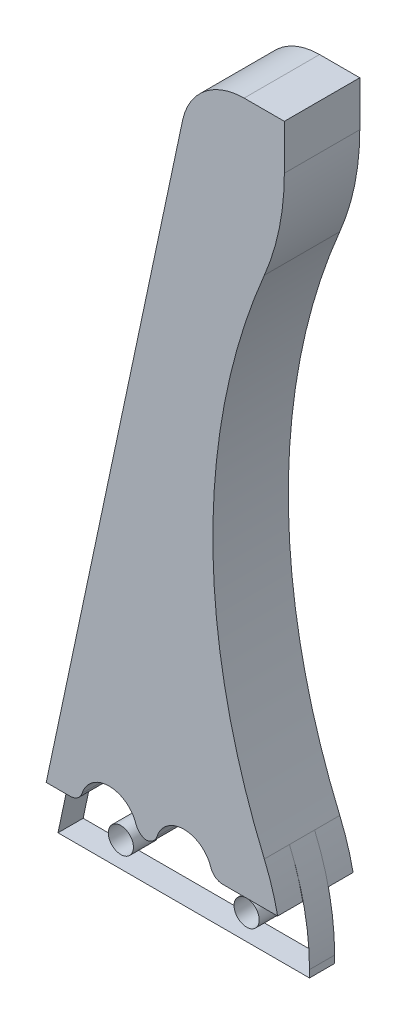
SolidWorks part; units mm, degrees
ref_plane "Alzado" through (0, 0, 0) normal (0, 0, 1) x (1, 0, 0)
ref_plane "Planta" through (0, 0, 0) normal (0, 1, 0) x (1, 0, 0)
ref_plane "Vista lateral" through (0, 0, 0) normal (1, 0, 0) x (0, 0, -1)
sketch "Croquis1" plane through (0, 0, 0) normal (0, 0, 1) x (1, 0, 0)
  line L0 (0, 0) -> (20, 0)
  line L5 (0, 0) -> (12.7534, 60)
  line L6 (12.7534, 60) -> (20, 60)
  line L7 (20, 60) -> (20, 52)
  line L8 (20, 0) -> (20, 5)
  arc A2 (20, 52) -> (20, 5) centre (65.7262, 28.5) ccw
  dimension "D5" = 60
  dimension "D1" = 78
  dimension "D2" = 20
  dimension "D3" = 5
  dimension "D4" = 8
  dimension "D6" = 0
extrude "Saliente-Extruir1" add sketch "Croquis1" along normal blind 2
fillet "Redondeo1" radius 5 1 edges at (12.7534, 60, 1)
fillet "Redondeo2" radius 20 1 edges at (20, 52, 1)
fillet "Redondeo3" radius 20 1 edges at (20, 5, 1)
sketch "Croquis3" plane through (0, 0, 2) normal (0, 0, 1) x (1, 0, 0)
  line L0 (0, 0) -> (20, 0) construction
  circle A0 centre (5, 2) radius 1
  circle A1 centre (15, 2) radius 1
  dimension "D1" = 2
  dimension "D2" = 2
  dimension "D3" = 5
  dimension "D5" = 10
  dimension "D4" = 2
extrude "Cortar-Extruir1" cut sketch "Croquis3" against normal blind 2
sketch "Croquis4" plane through (0, 0, 2) normal (0, 0, 1) x (1, 0, 0)
  line L0 (1.0628, 5) -> (19.4673, 5)
  line L1 (11.9116, 56.0396) -> (0, 0) construction
  line L2 (0, 0) -> (20, 0) construction
  line L3 (1.0628, 5) -> (11.9116, 56.0396)
  line L4 (16.8023, 60) -> (20, 60)
  line L5 (20, 60) -> (20, 56.4224)
  arc A1 (11.9116, 56.0396) -> (16.8023, 60) centre (16.8023, 55) cw
  arc A2 (20, 56.4224) -> (18.4078, 48.6022) centre (0, 56.4224) cw
  arc A3 (18.4078, 48.6022) -> (18.4078, 8.3978) centre (65.7262, 28.5) ccw
  arc A4 (18.4078, 8.3978) -> (19.4673, 5) centre (1.9082, 1.3883) cw
  dimension "D1" = 5
extrude "Saliente-Extruir2" add sketch "Croquis4" along normal blind 2 and the other way blind 4
sketch "Croquis5" plane through (0, 0, 4) normal (0, 0, 1) x (1, 0, 0)
  line L0 (1.0628, 5) -> (19.4673, 5) construction
  line L1 (3.8128, 5) -> (8.3128, 5)
  line L2 (9.7658, 5) -> (14.2658, 5)
  arc A0 (8.3128, 5) -> (3.8128, 5) centre (6.0628, 5) ccw
  arc A1 (3.8128, 5) -> (8.3128, 5) centre (6.0628, 5) cw
  arc A2 (9.7658, 5) -> (14.2658, 5) centre (12.0158, 5) cw
  dimension "D1" = 4.5
  dimension "D2" = 5
  dimension "D3" = 2
extrude "Cortar-Extruir2" cut sketch "Croquis5" against normal blind 2 contours L2 A2 | L1 A1
fillet "Redondeo4" radius 1 4 edges at (14.2658, 5, 3) (3.8128, 5, 3) (9.7658, 5, 3) (8.3128, 5, 3)
sketch "Croquis6" plane through (0, 0, -2) normal (0, 0, -1) x (-1, 0, 0)
  line L2 (-1.0628, 5) -> (-19.4673, 5) construction
  line L3 (-8.3128, 5) -> (-3.8128, 5)
  line L4 (-14.2428, 5) -> (-9.7428, 5)
  arc A1 (-3.8128, 5) -> (-8.3128, 5) centre (-6.0628, 5) ccw
  arc A2 (-8.3128, 5) -> (-3.8128, 5) centre (-6.0628, 5) cw
  arc A3 (-14.2428, 5) -> (-9.7428, 5) centre (-11.9928, 5) cw
  dimension "D1" = 4.5
  dimension "D2" = 5
  dimension "D3" = 2
extrude "Cortar-Extruir3" cut sketch "Croquis6" against normal blind 2 contours L3 A2 | L4 A3
fillet "Redondeo5" radius 1 4 edges at (14.2428, 5, -1) (9.7428, 5, -1) (8.3128, 5, -1) (3.8128, 5, -1)
